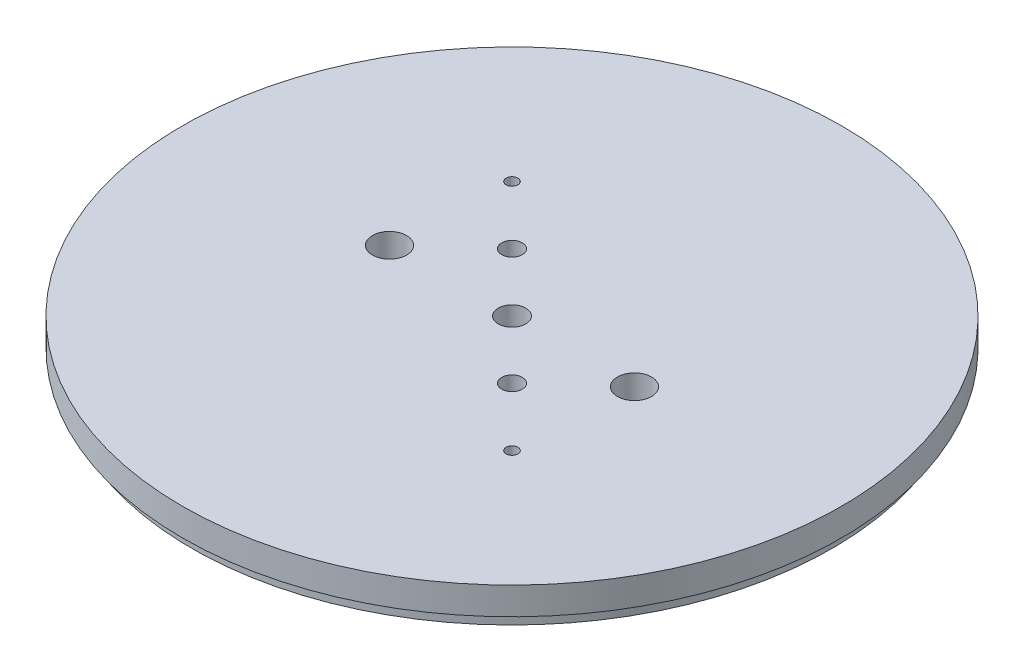
SolidWorks part; units mm, degrees
ref_plane "Front Plane" through (0, 0, 0) normal (0, 0, 1) x (1, 0, 0)
ref_plane "Top Plane" through (0, 0, 0) normal (0, 1, 0) x (1, 0, 0)
ref_plane "Right Plane" through (0, 0, 0) normal (1, 0, 0) x (0, 0, -1)
sketch "Sketch1" plane through (0, 0, 0) normal (0, 1, 0) x (1, 0, 0)
  line L0 (0, -76.2) -> (0, 76.2) construction
  line L1 (-76.2, 0) -> (76.2, 0) construction
  line L2 (-26.9408, 26.9408) -> (0, 0) construction
  line L3 (0, 56.7387) -> (0, 29.6936) construction
  line L4 (3.6407, 56.7387) -> (3.6407, 29.6936) construction
  line L5 (-3.6407, 56.7387) -> (-3.6407, 29.6936) construction
  line L6 (0, -56.7387) -> (0, -29.6936) construction
  line L7 (3.6407, -56.7387) -> (3.6407, -29.6936) construction
  line L8 (-3.6407, -56.7387) -> (-3.6407, -29.6936) construction
  line L9 (-53.8815, -53.8815) -> (54.3236, 54.3236) construction
  circle A0 centre (0, 0) radius 76.2
  circle A1 centre (0, 0) radius 3.175
  circle A2 centre (28.321, 0) radius 3.937
  circle A3 centre (-28.321, 0) radius 3.937
  circle A4 centre (-26.9408, 26.9408) radius 1.3589
  arc A6 (3.6407, 56.7387) -> (-3.6407, 56.7387) centre (0, 56.7387) ccw construction
  arc A7 (-3.6407, 29.6936) -> (3.6407, 29.6936) centre (0, 29.6936) ccw construction
  arc A8 (3.6407, -56.7387) -> (-3.6407, -56.7387) centre (0, -56.7387) cw construction
  arc A9 (-3.6407, -29.6936) -> (3.6407, -29.6936) centre (0, -29.6936) cw construction
  circle A10 centre (26.9408, -26.9408) radius 1.3589
  circle A11 centre (-13.4704, 13.4704) radius 2.3813
  circle A12 centre (13.4704, -13.4704) radius 2.3813
  point P16 (0, 43.2162)
  point P19 (0, 0)
  point P26 (0, -43.2162)
  point P35 (0, 0)
  point P36 (0, 0)
  dimension "D1" = 152.4
  dimension "D2" = 6.35
  dimension "D3" = 7.874
  dimension "D5" = 2.7178
  dimension "D8" = 4.7625
  dimension "D4" = 45
  dimension "D6" = 38.1
  dimension "D7" = 45
  dimension "D9" = 28.321
extrude "Boss-Extrude1" add sketch "Sketch1" along normal blind 9.525
sketch "Sketch2" plane through (0, 0, 0) normal (0, -1, 0) x (1, 0, 0)
  circle A0 centre (0, 0) radius 76.2
  circle A1 centre (0, 0) radius 74.041
  dimension "D1" = 152.4
  dimension "D2" = 148.082
extrude "Cut-Extrude1" cut sketch "Sketch2" against normal blind 3.175
sketch "Sketch3" plane through (0, 9.525, 0) normal (0, 1, 0) x (1, 0, 0)
  line L0 (0, 76.2) -> (0, -76.2) construction
  line L1 (-76.2, 0) -> (76.2, 0) construction
  line L2 (0, 34.798) -> (0, 13.97) construction
  line L3 (3.2385, 34.798) -> (3.2385, 13.97)
  line L4 (-3.2385, 34.798) -> (-3.2385, 13.97)
  line L5 (0, -34.798) -> (0, -13.97) construction
  line L6 (3.2385, -34.798) -> (3.2385, -13.97)
  line L7 (-3.2385, -34.798) -> (-3.2385, -13.97)
  circle A0 centre (0, 0) radius 76.2 construction
  arc A1 (3.2385, 34.798) -> (-3.2385, 34.798) centre (0, 34.798) ccw
  arc A2 (-3.2385, 13.97) -> (3.2385, 13.97) centre (0, 13.97) ccw
  arc A3 (3.2385, -34.798) -> (-3.2385, -34.798) centre (0, -34.798) cw
  arc A4 (-3.2385, -13.97) -> (3.2385, -13.97) centre (0, -13.97) cw
  point P7 (0, 13.97)
  point P8 (0, 34.798)
  point P12 (0, 24.384)
  point P17 (0, 0)
  point P20 (0, -24.384)
  point P25 (0, -34.798)
  point P26 (0, -13.97)
  dimension "D1" = 13.97
  dimension "D2" = 20.828
  dimension "D3" = 6.477
extrude "Cut-Extrude2" cut sketch "Sketch3" against normal blind 3.556 from offset 5.969 offset against normal yes
equation "\"leadDist\"=1.5"
